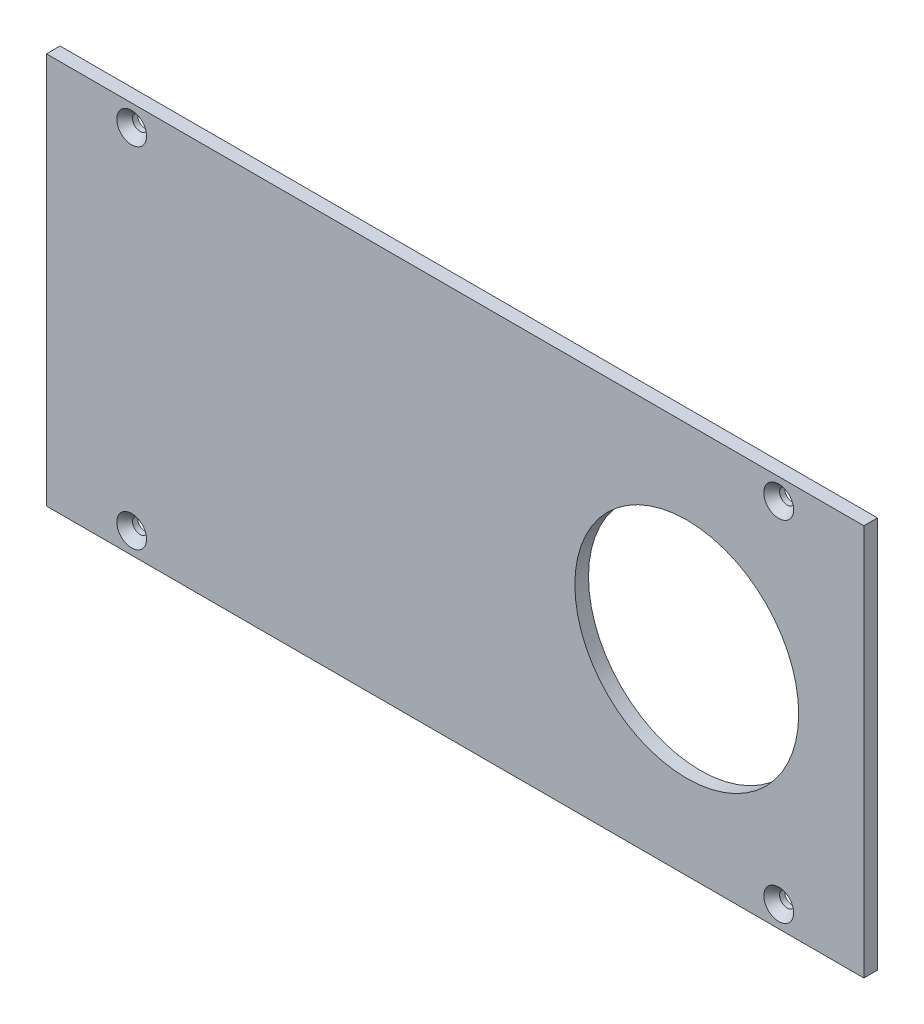
SolidWorks part; units mm, degrees
material "6061-T4 (SS)"
ref_plane "Front Plane" through (0, 0, 0) normal (0, 0, 1) x (1, 0, 0)
ref_plane "Top Plane" through (0, 0, 0) normal (0, 1, 0) x (1, 0, 0)
ref_plane "Right Plane" through (0, 0, 0) normal (1, 0, 0) x (0, 0, -1)
sketch "Sketch1" plane through (0, 0, 0) normal (0, 0, 1) x (1, 0, 0)
  line L1 (0, 0) -> (96, 0)
  line L2 (0, 0) -> (0, 46)
  line L3 (0, 46) -> (96, 46)
  line L4 (96, 0) -> (96, 46)
  dimension "D1" = 46
  dimension "D2" = 96
extrude "Boss-Extrude1" add sketch "Sketch1" along normal blind 1.6002
sketch "Sketch2" plane through (0, 0, 1.6002) normal (0, 0, 1) x (1, 0, 0)
  circle A0 centre (75.2, 23.05) radius 13.1445
  circle A1 centre (75.2, 23.05) radius 13.1445 construction
extrude "Cut-Extrude1" cut sketch "Sketch2" against normal through all
hole_wizard "CSK for #0 Flat Head Socket Cap Screw1" positions "Sketch6" profile "Sketch7" countersink size "#0" standard "ANSI Inch" end condition through all
sketch "Sketch6" plane through (0, 0, 1.6002) normal (0, 0, 1) x (1, 0, 0)
  line L0 (0, 46) -> (0, 0) construction
  line L1 (10, 43.5) -> (10, 2.5) construction
  line L2 (10, 2.5) -> (86, 2.5) construction
  line L3 (86, 2.5) -> (86, 43.5) construction
  line L4 (86, 43.5) -> (10, 43.5) construction
  line L6 (96, 0) -> (96, 46) construction
  line L8 (96, 46) -> (0, 46) construction
  line L9 (0, 0) -> (96, 0) construction
  point P0 (10, 43.5)
  point P2 (10, 2.5)
  point P4 (86, 2.5)
  point P6 (86, 43.5)
  dimension "D1" = 10
  dimension "D2" = 10
  dimension "D3" = 2.5
  dimension "D4" = 2.5
sketch "Sketch7" plane through (10, 43.5, 1.6002) normal (1, 0, 0) x (0, -1, 0)
  line L0 (0, 0) -> (0, 1.6002)
  line L1 (0, 1.6002) -> (0.889, 1.6002)
  line L2 (0.889, 1.6002) -> (0.889, 0.9935)
  line L3 (0.889, 0.9935) -> (1.7526, 0)
  line L5 (1.7526, 0) -> (0, 0)
  line L6 (-0.889, 0.9935) -> (-1.7526, 0) construction
  line L11 (0, -6.35) -> (0, 107.95) construction
  dimension "Thru Hole Dia." = 1.778
  dimension "Thru Hole Depth" = 1.6002
  dimension "Near C'Sink Dia." = 3.5052
  dimension "Near C'Sink Angle" = 82
